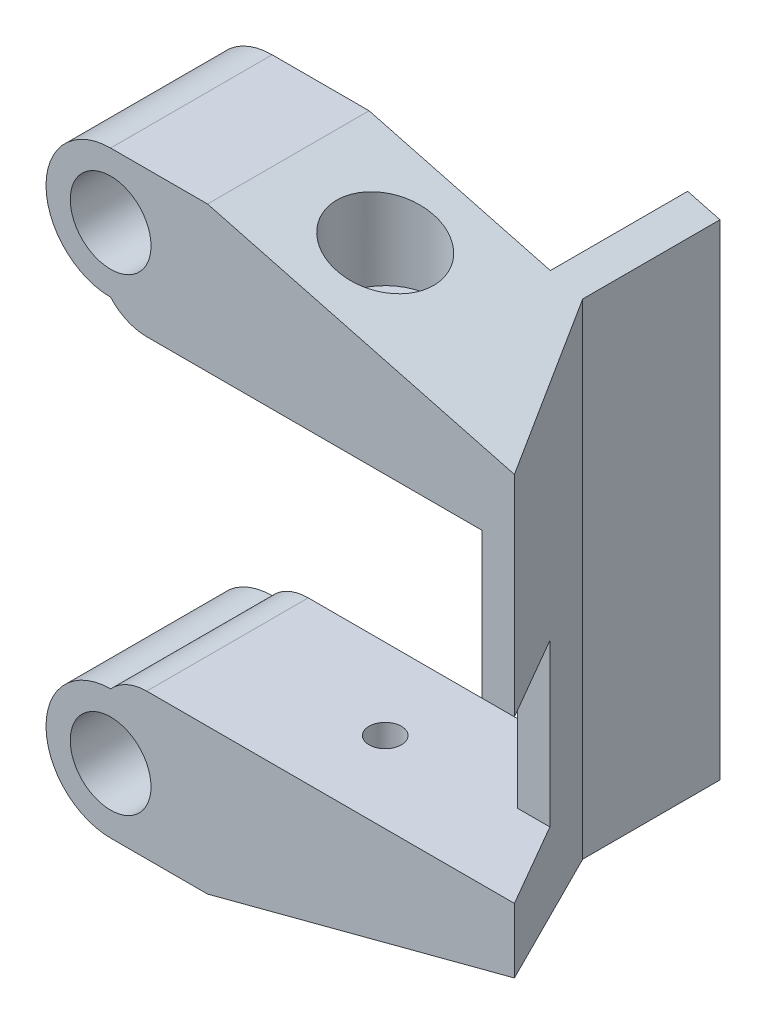
SolidWorks part; units mm, degrees
ref_plane "Alzado" through (0, 0, 0) normal (0, 0, 1) x (1, 0, 0)
ref_plane "Planta" through (0, 0, 0) normal (0, 1, 0) x (1, 0, 0)
ref_plane "Vista lateral" through (0, 0, 0) normal (1, 0, 0) x (0, 0, -1)
sketch "Croquis1" plane through (0, 0, 0) normal (0, 0, 1) x (1, 0, 0)
  line L5 (-106.2316, 22.7007) -> (-131.2316, 22.7007)
  line L6 (-131.2316, 22.7007) -> (-131.2316, 21.7007)
  line L7 (-106.2316, 22.7007) -> (-106.2316, 18.7007)
  line L8 (-106.2316, 18.7007) -> (-125.2316, 18.7007)
  line L9 (-125.2316, 18.7007) -> (-125.2316, 13.7007)
  line L10 (-125.2316, 13.7007) -> (-131.2316, 13.7007)
  circle A0 centre (-131.2316, 17.7007) radius 2.5
  arc A2 (-131.2316, 21.7007) -> (-131.2316, 13.7007) centre (-131.2316, 17.7007) ccw
  dimension "D1" = 4
  dimension "D2" = 5
  dimension "D3" = 6
  dimension "D4" = 5
  dimension "D5" = 25
  dimension "D6" = 5
extrude "Saliente-Extruir1" add sketch "Croquis1" along normal blind 10
sketch "Croquis2" plane through (0, 18.7007, 0) normal (0, -1, 0) x (1, 0, 0)
  line L1 (-106.2316, 0) -> (-106.2316, 10)
  line L2 (-106.2316, 10) -> (-112.0051, 0)
  line L4 (-112.0051, 0) -> (-106.2316, 0)
  line L5 (-125.2316, 10) -> (-125.2316, 0) construction
  line L6 (-106.2316, 10) -> (-106.2316, 0) construction
  circle A0 centre (-119.2316, 5) radius 1
  dimension "D1" = 6
  dimension "D2" = 30
  dimension "D3" = 0
extrude "Cortar-Extruir1" cut sketch "Croquis2" against normal up to vertex (4 mm away) up to point (-106.2316, 22.7007, 10)
sketch "Croquis3" plane through (0, 18.7007, 0) normal (0, -1, 0) x (1, 0, 0)
  line L0 (-106.2316, 10) -> (-108.2316, 10)
  line L1 (-108.2316, 10) -> (-114.0051, 0)
  line L2 (-114.0051, 0) -> (-112.0051, 0)
  line L3 (-106.2316, 10) -> (-112.0051, 0)
  dimension "D1" = 2
  dimension "D2" = 2
extrude "Saliente-Extruir2" add sketch "Croquis3" against normal blind 13.5
sketch "Croquis4" plane through (0, 18.7007, 0) normal (0, -1, 0) x (1, 0, 0)
  circle A0 centre (-119.2316, 5) radius 3
extrude "Cortar-Extruir2" cut sketch "Croquis4" against normal blind 1
sketch "Croquis5" plane through (0, 0, 10) normal (0, 0, 1) x (1, 0, 0)
  line L0 (-106.2316, 18.7007) -> (-106.2316, 32.2007) construction
  line L1 (-108.2316, 22.7007) -> (-106.2316, 22.7007)
  line L2 (-108.2316, 22.7007) -> (-108.2316, 32.7007)
  line L3 (-108.2316, 32.7007) -> (-106.2316, 32.7007)
  line L4 (-106.2316, 22.7007) -> (-106.2316, 32.7007)
  dimension "D1" = 10
sketch "Croquis6" plane through (0, 18.7007, 0) normal (0, -1, 0) x (1, 0, 0)
  line L0 (-106.2316, 10) -> (-125.2316, 10)
  line L1 (-125.2316, 10) -> (-125.2316, 0)
  line L2 (-125.2316, 0) -> (-112.0051, 0)
  line L3 (-112.0051, 0) -> (-106.2316, 10)
  circle A0 centre (-119.2316, 5) radius 3
extrude "Saliente-Extruir3" add sketch "Croquis6" along normal up to vertex (5 mm away) up to point (-125.2316, 13.7007, 10)
sketch "Croquis7" plane through (0, 0, 10) normal (0, 0, 1) x (1, 0, 0)
  line L0 (-106.2316, 18.7007) -> (-106.2316, 13.7007)
  line L1 (-106.2316, 13.7007) -> (-106.2316, 32.2007) construction
  line L2 (-106.2316, 13.7007) -> (-125.2316, 13.7007)
  line L3 (-131.2316, 13.7007) -> (-106.2316, 13.7007) construction
  line L4 (-125.2316, 13.7007) -> (-106.2316, 18.7007)
  line L5 (-108.2316, 22.7007) -> (-131.2316, 22.7007) construction
  dimension "D1" = 4
  dimension "D2" = 19
extrude "Cortar-Extruir3" cut sketch "Croquis7" against normal up to vertex (10 mm away) up to point (-112.0051, 13.7007, 0)
sketch "Croquis8" plane through (0, 0, 0) normal (0, 0, -1) x (-1, 0, 0)
  line L0 (112.0051, 17.1813) -> (112.0051, 32.2007)
  line L1 (112.0051, 32.2007) -> (114.0051, 32.2007)
  line L2 (114.0051, 32.2007) -> (114.0051, 16.655)
  line L3 (112.0051, 17.1813) -> (125.2316, 13.7007) construction
  line L4 (114.0051, 16.655) -> (112.0051, 17.1813)
extrude "Saliente-Extruir4" add sketch "Croquis8" along normal blind 8.5
mirror "Simetría1" about plane through (0, 32.2007, 0) normal (0, -1, 0) of bodies 110
extrude "Cortar-Extruir4" cut sketch "Croquis5" along direction (-0.5, 0, -0.866) on the side against the normal blind 6
fillet "Redondeo1" radius 3 2 edges at (-131.2316, 41.7007, 5) (-131.2316, 22.7007, 5)
